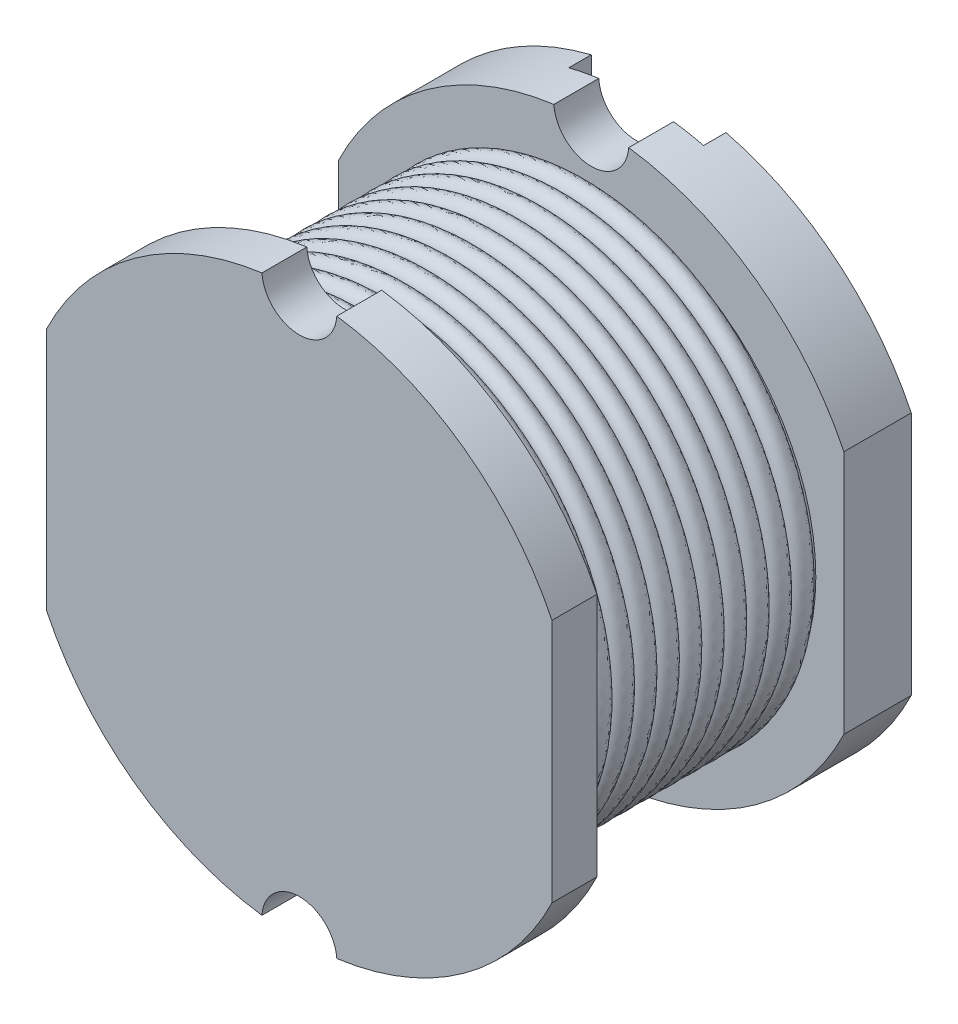
SolidWorks part; units mm, degrees
ref_plane "Front Plane" through (0, 0, 0) normal (0, 0, 1) x (1, 0, 0)
ref_plane "Top Plane" through (0, 0, 0) normal (0, 1, 0) x (1, 0, 0)
ref_plane "Right Plane" through (0, 0, 0) normal (1, 0, 0) x (0, 0, -1)
sketch "Sketch1" plane through (0, 0, 0) normal (0, 0, 1) x (1, 0, 0)
  circle A0 centre (0, 0) radius 2.5
  dimension "D1" = 5
extrude "Boss-Extrude1" add sketch "Sketch1" along normal blind 3.2 contours A0
sketch "Sketch2" plane through (0, 0, 0) normal (0, 0, -1) x (-1, 0, 0)
  line L0 (0, 0) -> (0, 3.8972) construction
  line L1 (-3.4978, -2.8614) -> (-2.25, -2.8614)
  line L2 (-3.4978, -2.8614) -> (-3.4978, 2.8614)
  line L3 (-3.4978, 2.8614) -> (-2.25, 2.8614)
  line L4 (-2.25, -2.8614) -> (-2.25, 2.8614)
  line L5 (-3.4978, -2.8614) -> (-2.25, 2.8614) construction
  line L6 (-3.4978, 2.8614) -> (-2.25, -2.8614) construction
  line L7 (3.4978, -2.8614) -> (2.25, -2.8614)
  line L8 (3.4978, 2.8614) -> (2.25, -2.8614) construction
  line L9 (3.4978, -2.8614) -> (2.25, 2.8614) construction
  line L10 (2.25, -2.8614) -> (2.25, 2.8614)
  line L11 (3.4978, 2.8614) -> (2.25, 2.8614)
  line L12 (3.4978, -2.8614) -> (3.4978, 2.8614)
  line L13 (-2.8739, 0) -> (2.8739, 0) construction
  circle A0 centre (0, 2.5) radius 0.3341
  circle A1 centre (0, 0) radius 2.5 construction
  circle A2 centre (0, -2.5) radius 0.3341
  point P0 (-2.8739, 0)
  dimension "D1" = 4.5
extrude "Cut-Extrude1" cut sketch "Sketch2" against normal through all
sketch "Sketch3" plane through (0, 0, 0) normal (0, 0, -1) x (-1, 0, 0)
  line L1 (-0.6, -2.5) -> (0.6, -2.5)
  line L2 (-0.6, -2.5) -> (-0.6, 2.5)
  line L3 (-0.6, 2.5) -> (0.6, 2.5)
  line L4 (0.6, -2.5) -> (0.6, 2.5)
  line L5 (-0.6, -2.5) -> (0.6, 2.5) construction
  line L6 (-0.6, 2.5) -> (0.6, -2.5) construction
  arc A0 (-0.3334, 2.4777) -> (-2.25, 1.0897) centre (0, 0) ccw construction
  point P0 (0, 0)
  dimension "D1" = 1.2
extrude "Cut-Extrude2" cut sketch "Sketch3" against normal blind 0.2
ref_plane "Plane1" through (0, 0, 1.6) normal (0, 0, 1) x (1, 0, 0)
sketch "Sketch5" plane through (0, 0, 1.6) normal (0, 0, 1) x (1, 0, 0)
  circle A0 centre (0, 0) radius 2
  circle A1 centre (0, 0) radius 3.0203
  dimension "D1" = 4
extrude "Cut-Extrude3" cut sketch "Sketch5" along normal offset from surface 0.4 and the other way offset from surface (1 mm away) 0.6 up to face at (0, 0, 3.2) other way up to face at (-1.4995, 0, 0)
ref_plane "Plane3" through (0, 0, 0.6) normal (0, 0, 1) x (1, 0, 0)
sketch "Sketch28" plane through (0, 0, 0) normal (1, 0, 0) x (0, 0, -1)
  circle A0 centre (-0.6, -2) radius 0.0954
sketch "Sketch29" plane through (0, 0, 0.6) normal (0, 0, 1) x (1, 0, 0)
  circle A0 centre (0, 0) radius 2
curve "Helix/Spiral2" pitch 0.2 height 2.3 turns 11.5
sweep "Sweep8" add profiles "Sketch28" path "Helix/Spiral2"
